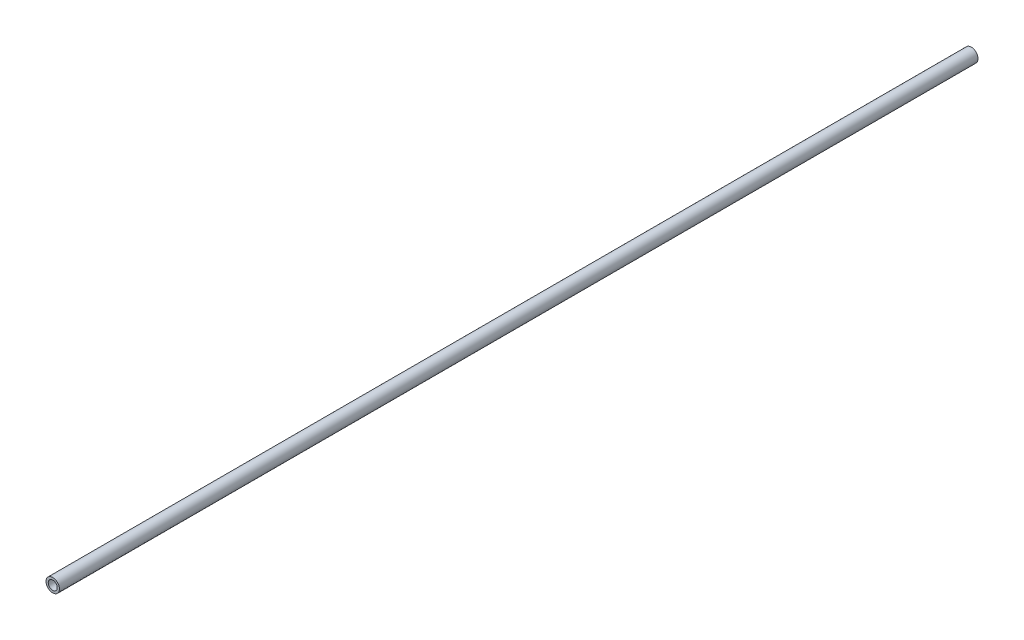
SolidWorks part; units mm, degrees
material "CarbonFiber"
ref_plane "Спереди" through (0, 0, 0) normal (0, 0, 1) x (1, 0, 0)
ref_plane "Сверху" through (0, 0, 0) normal (0, 1, 0) x (1, 0, 0)
ref_plane "Справа" through (0, 0, 0) normal (1, 0, 0) x (0, 0, -1)
sketch "Эскиз1" plane through (0, 0, 0) normal (0, 0, 1) x (1, 0, 0)
  circle A0 centre (0, 0) radius 3
  circle A1 centre (0, 0) radius 2
  dimension "D1" = 6
  dimension "D2" = 1
extrude "Бобышка-Вытянуть1" add sketch "Эскиз1" along normal mid plane 410
equation "\"DTailTube\"= 16mm'Диаметр трубки хвостового оперения"
equation "\"FusLenght\"= 700mm"
equation "\"DMotor\"= 35.2mm"
equation "\"MotorArm\"= 320mm"
equation "\"DFus\"= 150mm"
equation "\"DFusTube\"= 30mm'Диаметр трубки внутри фюзеляжа"
equation "\"FusTubeHeight\"= 40mm"
equation "\"FusCentralPartLenght\"= 410mm"
equation "\"FusNoseLenght\"= 150mm"
equation "\"WingOffset\"= 1mm'Расстояние от внутренней поверхности фюзеляжа до профиля крыла по вертикали"
equation "\"EllipseRatio\"= 0.95'Центральная часть фюзеляжа - эллипс. Этот параметр - отношение длин осей эллипса"
equation "\"FrameOffset\"= 0.6mm"
equation "\"DThreadedInsert\"= 3mm'Внешний диамер резьбовых втулок"
equation "\"CenterSectionLenght\"= 140mm'Длина центроплана"
equation "\"b\"= 1700mm'Размах"
equation "\"cwr\"= 236mm'Корневая хорда крыла"
equation "\"TR\"= 0.75'Сужение крыла"
equation "\"cwt\"= \"TR\" * \"cwr\"'Концевая хорда крыла"
equation "\"DWingMainSpar\"= 16mm'Диаметр главного лонжерона крыла"
equation "\"DWingSecondSpar\"= 8mm'Диаметр второго лонжерона крыла"
equation "\"WingSparsDistance\"= 80mm'Расстояния между отверстиями по лонжерон крыла"
equation "\"c\"= 210mm'САХ крыла"
equation "\"FusTubeLenght\"= \"FusLenght\"-90mm'Длина трубки фюзеляжа"
equation "\"bt\"=291mm'Высота лопатки хвоста"
equation "\"TailTubeLenght\"=680mm'Длина хвостовой балки"
equation "\"DStringer\"=6mm'Диаметр стрингеров"
equation "\"D1@Эскиз1\"=\"DStringer\""
equation "\"D1@Бобышка-Вытянуть1\"=\"FusCentralPartLenght\""
equation "\"TailConnectorBaseLenght\"=20mm'Высота основания конектора хвоста"
equation "\"CargoHolderHoleDistance\"=30mm'Расстояние между крепежными отверстиями для держателя груза"
equation "\"FuselageThickness\"=1.2mm'Толщина фюзеляжа"
equation "\"ct\"=182mm'Корневая хорда хвоста"
equation "\"lambda_t\"=0.3'Доля хвоста, занатая рулем высоты"
equation "\"DTailSpar\"=6mm'Диаметр лонжерона хвостового оперения"
equation "\"TailSparDistance\"=40mm'Расстояние между лонжеронами хвостового оперения"
equation "\"CrossSectionWidth\"=15mm'Ширина кольцевой части шпангоута"
